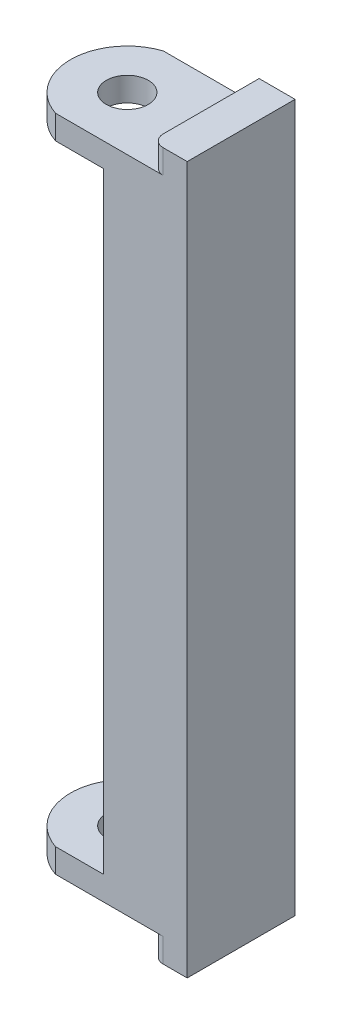
SolidWorks part; units mm, degrees
ref_plane "Front Plane" through (0, 0, 0) normal (0, 0, 1) x (1, 0, 0)
ref_plane "Top Plane" through (0, 0, 0) normal (0, 1, 0) x (1, 0, 0)
ref_plane "Right Plane" through (0, 0, 0) normal (1, 0, 0) x (0, 0, -1)
sketch "Sketch1" plane through (0, 0, 0) normal (0, 1, 0) x (1, 0, 0)
  line L0 (-2.5, 0) -> (2.5, 0) construction
  line L5 (-3.991, 4.5) -> (4, 4.5)
  line L6 (-3.991, -4.5) -> (4, -4.5)
  line L8 (7, -4.5) -> (7, 4.5)
  line L10 (5.0195, 4.5) -> (4, 4.5)
  line L11 (7, -4.5) -> (5, -4.5)
  line L12 (7, -4.5) -> (7, 4.5)
  line L13 (7, 4.5) -> (5.0195, 4.5)
  line L14 (4, -3.5) -> (4, 4.5)
  line L15 (5, -4.5) -> (4, -4.5)
  arc A1 (-3.991, 4.5) -> (-3.991, -4.5) centre (-2.5, 0) ccw
  circle A3 centre (-2.5, 0) radius 1.75
  arc A4 (0.0045, 4.5) -> (0.0045, -4.5) centre (-2.5, 0) cw
  arc A6 (5, -4.5) -> (4, -3.5) centre (5, -3.5) cw
  point P2 (0, 0)
  dimension "D2" = 9.5
  dimension "D3" = 3.5
  dimension "D6" = 5.15
  dimension "D8" = 1
  dimension "D1" = 9
  dimension "D4" = 5
  dimension "D5" = 2.5
  dimension "D7" = 3
extrude "Boss-Extrude3" add sketch "Sketch1" along normal blind 2 contours A4 L5 A1 L6 A3 | L5 A4 L6 | L12 L13 L10 L14 A6 L11 region at (-1.9933, 0, -4.3663) region at (2.8287, 0, 0.0477)
extrude "Boss-Extrude4" add sketch "Sketch1<3>" against normal blind 25.5 contours L5 A4 L6 | L12 L13 L10 L14 A6 L11 region at (2.8287, 0, 0.0477)
sketch "Sketch1<3>" plane through (0, 0, 0) normal (0, 1, 0) x (1, 0, 0) same geometry as "Sketch1"
extrude "Boss-Extrude5" add sketch "Sketch1<5>" along normal blind 4 contours L13 L14 L11 L8 region at (5.5102, 0, -0.0343)
sketch "Sketch1<5>" plane through (0, 0, 0) normal (0, 1, 0) x (1, 0, 0) same geometry as "Sketch1"
mirror "Mirror1" about plane through (0, -25.5, 0) normal (0, 1, 0) of bodies 111
